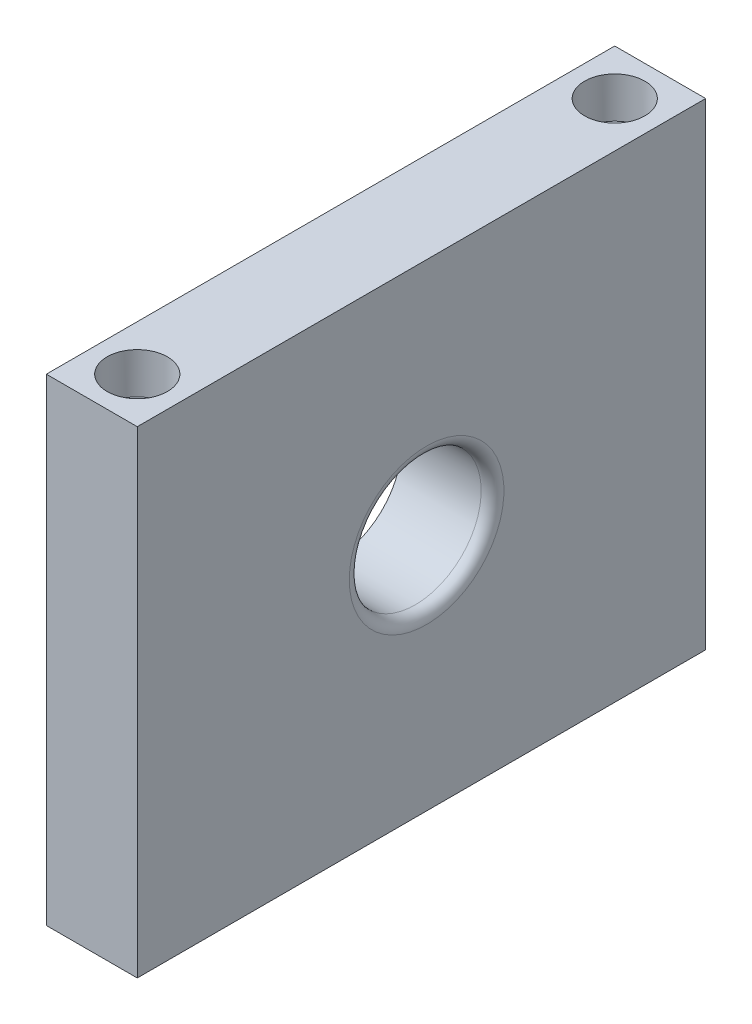
SolidWorks part; units mm, degrees
ref_plane "Front Plane" through (0, 0, 0) normal (0, 0, 1) x (1, 0, 0)
ref_plane "Top Plane" through (0, 0, 0) normal (0, 1, 0) x (1, 0, 0)
ref_plane "Right Plane" through (0, 0, 0) normal (1, 0, 0) x (0, 0, -1)
sketch "Sketch1" plane through (0, 0, 0) normal (0, 1, 0) x (1, 0, 0)
  line L1 (-10.223, 36.3848) -> (14.777, 36.3848)
  line L2 (-10.223, 36.3848) -> (-10.223, -13.6152)
  line L3 (-10.223, -13.6152) -> (14.777, -13.6152)
  line L4 (14.777, 36.3848) -> (14.777, -13.6152)
  circle A0 centre (1.277, 11.3848) radius 3.4
  dimension "D3" = 6.8
  dimension "D1" = 50
  dimension "D2" = 25
  dimension "D4" = 13.5
  dimension "D5" = 25
extrude "Boss-Extrude1" add sketch "Sketch1" along normal blind 3
sketch "Sketch2" plane through (-10.223, 0, 0) normal (-1, 0, 0) x (0, 0, 1)
  line L0 (18.15, 0) -> (-18.15, 0) construction
  line L1 (-36.3848, 3) -> (13.6152, 3)
  line L2 (-36.3848, 3) -> (-36.3848, 0)
  line L3 (-36.3848, 0) -> (13.6152, 0)
  line L4 (13.6152, 3) -> (13.6152, 0)
  line L5 (13.6152, 3) -> (13.6152, 0) construction
extrude "Boss-Extrude2" add sketch "Sketch2" along normal blind 8
sketch "Sketch3" plane through (0, 0, 0) normal (0, -1, 0) x (1, 0, 0)
  line L0 (-18.223, 13.6152) -> (14.777, 13.6152) construction
  line L1 (-18.223, -36.3848) -> (-10.223, -36.3848)
  line L2 (-18.223, -36.3848) -> (-18.223, 13.6152)
  line L3 (-18.223, 13.6152) -> (-10.223, 13.6152)
  line L4 (-10.223, -36.3848) -> (-10.223, 13.6152)
  dimension "D1" = 8
extrude "Boss-Extrude3" add sketch "Sketch3" along normal blind 42
sketch "Sketch4" plane through (0, 3, 0) normal (0, 1, 0) x (1, 0, 0)
  line L0 (-18.223, -13.6152) -> (-18.223, 36.3848) construction
  line L1 (14.777, 36.3848) -> (-18.223, 36.3848) construction
  line L2 (-18.223, -13.6152) -> (14.777, -13.6152) construction
  circle A0 centre (-14.223, 32.3848) radius 2.65
  circle A1 centre (-14.223, -9.6152) radius 2.65
  dimension "D2" = 5.3
  dimension "D4" = 5.3
  dimension "D5" = 4
  dimension "D6" = 4
  dimension "D1" = 4
  dimension "D3" = 4
extrude "Cut-Extrude1" cut sketch "Sketch4" against normal blind 6.6
ref_plane "Plane1" through (0, -19.5, 0) normal (0, 1, 0) x (1, 0, 0)
mirror "Mirror1" about plane through (0, -19.5, 0) normal (0, 1, 0) of "Cut-Extrude1"
sketch "Sketch5" plane through (-18.223, 0, 0) normal (-1, 0, 0) x (0, 0, 1)
  line L0 (18.15, 0) -> (-18.15, 0) construction
  line L1 (-6.9841, -24.1818) -> (-6.6547, -18.3888) construction
  line L2 (-6.6547, -18.3888) -> (-11.5069, -15.207) construction
  line L3 (-11.5069, -15.207) -> (-16.6885, -17.8182) construction
  line L4 (-16.6885, -17.8182) -> (-17.0179, -23.6112) construction
  line L5 (-17.0179, -23.6112) -> (-12.1657, -26.793) construction
  line L6 (-12.1657, -26.793) -> (-6.9841, -24.1818) construction
  circle A0 centre (-11.8363, -21) radius 5.025 construction
  circle A1 centre (-11.8363, -21) radius 5.8024
  dimension "D1" = 21
  dimension "D2" = 10.05
extrude "Cut-Extrude2" cut sketch "Sketch5" against normal blind 9
fillet "Fillet2" radius 1 1 edges at (-10.223, -21, -6.0339)
ref_plane "Plane2" through (-1.723, 0, 0) normal (-1, 0, 0) x (0, 0, 1)
mirror "Mirror2" about plane through (-1.723, 0, 0) normal (-1, 0, 0) of "Cut-Extrude1"
sketch "Sketch6" plane through (0, 3, 0) normal (0, 1, 0) x (1, 0, 0)
  line L0 (1.277, 14.7848) -> (1.277, 7.9848) construction
  line L1 (14.777, -13.6152) -> (14.777, 36.3848) construction
  line L2 (14.777, 16.9444) -> (14.777, 5.8251)
  circle A0 centre (1.277, 11.3848) radius 3.4 construction
  circle A1 centre (1.277, 11.3848) radius 3.1
  circle A2 centre (1.277, 11.3848) radius 12.6
  arc A3 (14.777, 16.9444) -> (14.777, 5.8251) centre (1.277, 11.3848) ccw
  line M9 (14.777, -13.6152) -> (14.777, 36.3848)
  dimension "D1" = 25.2
  dimension "D2" = 2
extrude "Boss-Extrude4" add sketch "Sketch6" along normal blind 2 contours A3 A2 M9
fillet "Fillet4" radius 1 1 edges at (14.777, 5, -11.3848)
sketch "Sketch8" plane through (0, 3, 0) normal (0, 1, 0) x (1, 0, 0)
  line L0 (4.677, 11.3848) -> (-2.123, 11.3848) construction
  circle A0 centre (1.277, 11.3848) radius 3.4 construction
  circle A1 centre (1.277, 19.8848) radius 1.5898
  circle A2 centre (1.277, 2.8848) radius 1.7774
  point P9 (1.277, 11.3848)
  dimension "D1" = 8.5
  dimension "D2" = 8.5
extrude "Cut-Extrude3" cut sketch "Sketch8" against normal blind 10
sketch "Sketch9" plane through (0, 0, 13.6152) normal (0, 0, 1) x (1, 0, 0)
  line L1 (14.777, 0) -> (-34.2447, 0)
  line L2 (14.777, 0) -> (14.777, 20.9769)
  line L3 (14.777, 20.9769) -> (-34.2447, 20.9769)
  line L4 (-34.2447, 0) -> (-34.2447, 20.9769)
extrude "Cut-Extrude4" cut sketch "Sketch9" against normal through all
